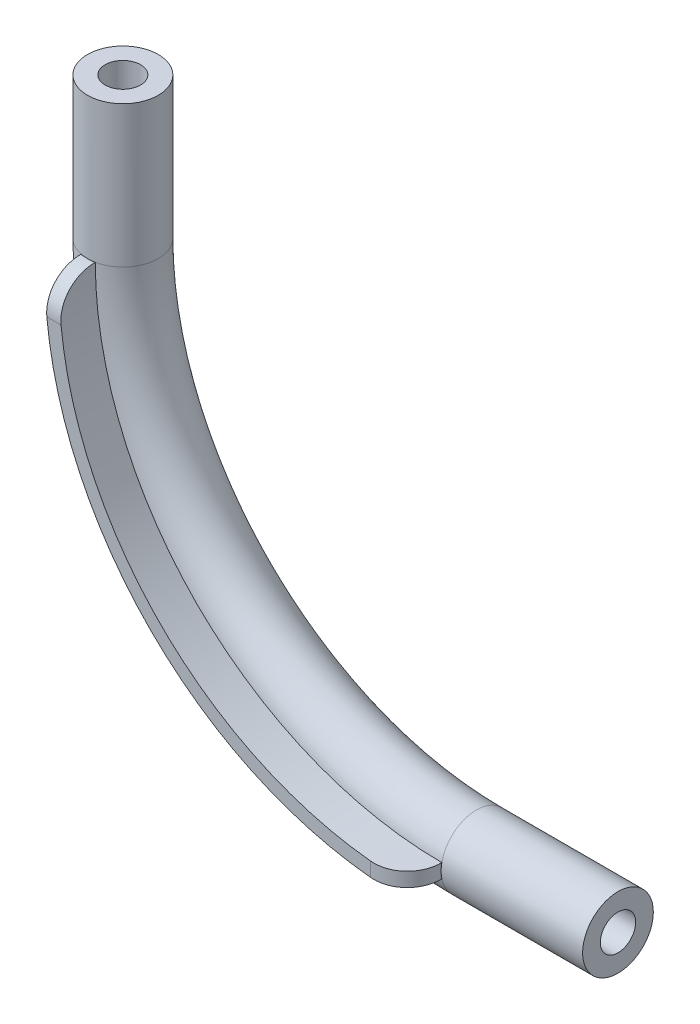
SolidWorks part; units mm, degrees
ref_plane "前基準面" through (0, 0, 0) normal (0, 0, 1) x (1, 0, 0)
ref_plane "上基準面" through (0, 0, 0) normal (0, 1, 0) x (1, 0, 0)
ref_plane "右基準面" through (0, 0, 0) normal (1, 0, 0) x (0, 0, -1)
sketch "草圖4" plane through (0, 0, 0) normal (0, 1, 0) x (1, 0, 0)
  line L0 (0, 3.4749) -> (0, -3.49) construction
  line L1 (0, -55) -> (0, 55) construction
  line L2 (-55, 0) -> (55, 0) construction
  circle A0 centre (-50, 0) radius 5
  dimension "D1" = 50
  dimension "D2" = 10
revolve "旋轉1" add sketch "草圖4" angle 90 about L0
sketch "草圖5" plane through (0, 0, 0) normal (1, 0, 0) x (0, 0, -1)
  circle A0 centre (0, -50) radius 5 construction
  circle A1 centre (0, -50) radius 5
  circle A2 centre (0, -50) radius 2.5
  dimension "D1" = 5
extrude "填料-伸長4" add sketch "草圖5" along normal blind 20 contours A1 | A2
sketch "草圖6" plane through (0, 0, 0) normal (0, 1, 0) x (1, 0, 0)
  circle A0 centre (-50, 0) radius 5 construction
  circle A1 centre (-50, 0) radius 5
  circle A2 centre (-50, 0) radius 2.5
  dimension "D1" = 5
extrude "填料-伸長5" add sketch "草圖6" along normal blind 20
sketch "草圖7" plane through (0, 0, 0) normal (0, 0, 1) x (1, 0, 0)
  line L0 (10.0499, -50) -> (-4.9615, -50) construction
  line L2 (-3.7268, -49) -> (6.7893, -49) construction
  line L3 (-3.7268, -51) -> (6.7893, -51) construction
  line L4 (-49, 0) -> (-51, 0)
  line L5 (0, -49) -> (0, -51)
  arc A0 (-49, 0) -> (0, -49) centre (0, 0) ccw
  arc A1 (-51, 0) -> (0, -51) centre (0, 0) ccw
  dimension "D1" = 1
extrude "填料-伸長6" add sketch "草圖7" along normal blind 10
fillet "圓角1" radius 5 2 edges at (0, -50, 10) (-50, 0, 10)
sketch "草圖8" plane through (0, 20, 0) normal (0, 1, 0) x (1, 0, 0)
  line L0 (-50, 5) -> (-50, -5) construction
  line L1 (-50, -5) -> (-49, -5) construction
  circle A0 centre (-50, 0) radius 5 construction
  point P7 (-50, 0)
sketch "草圖9" plane through (20, 0, 0) normal (1, 0, 0) x (0, 0, -1)
  line L0 (0, -45) -> (0, -55) construction
  line L1 (0, 41.25) -> (0, -41.25) construction
  circle A0 centre (0, -50) radius 5 construction
  point P6 (0, -50)
